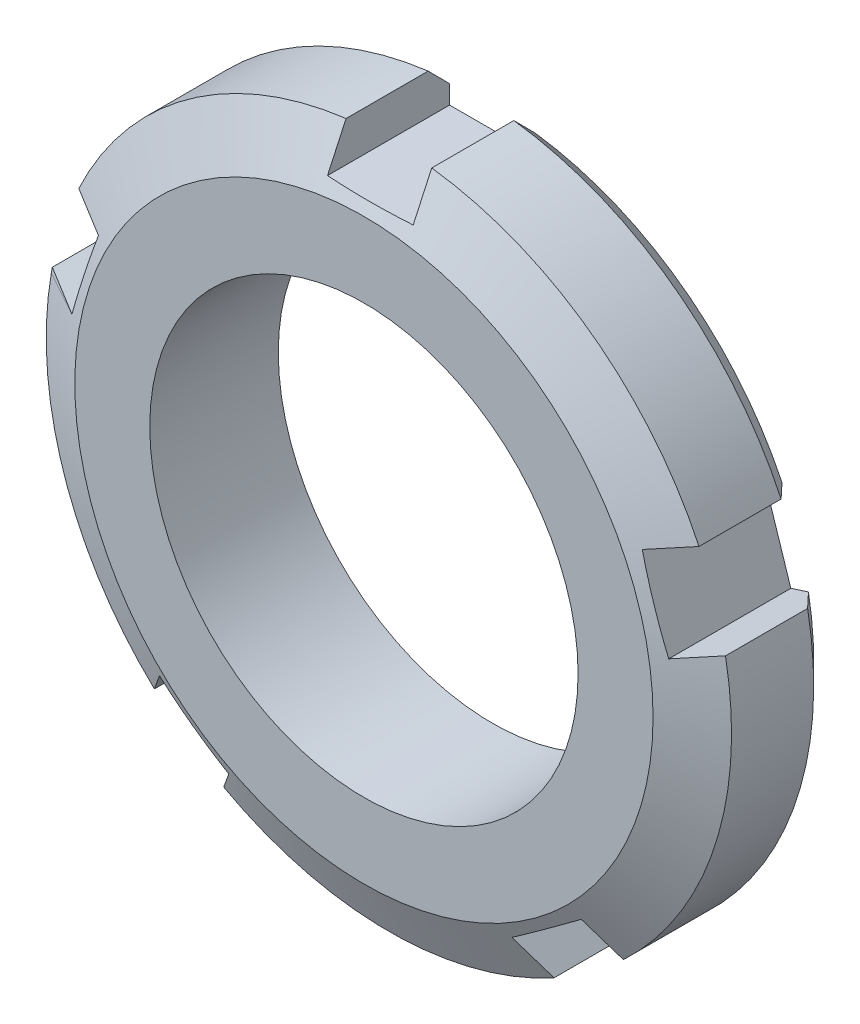
SolidWorks part; units mm, degrees
ref_plane "Front Plane" through (0, 0, 0) normal (0, 0, 1) x (1, 0, 0)
ref_plane "Top Plane" through (0, 0, 0) normal (0, 1, 0) x (1, 0, 0)
ref_plane "Right Plane" through (0, 0, 0) normal (1, 0, 0) x (0, 0, -1)
sketch "Sketch1" plane through (0, 0, 0) normal (1, 0, 0) x (0, 0, -1)
  line L0 (-16.3452, 0) -> (34.4162, 0) construction
  line L1 (0, 10) -> (6, 10)
  line L2 (6, 10) -> (6, 15)
  line L3 (6, 15) -> (5, 16)
  line L4 (5, 16) -> (1.1658, 16)
  line L5 (1.1658, 16) -> (0, 13.5)
  line L6 (0, 13.5) -> (0, 10)
  dimension "D1" = 20
  dimension "D2" = 32
  dimension "D3" = 6
  dimension "D4" = 45
  dimension "D5" = 25
  dimension "D6" = 2.5
  dimension "D7" = 1
revolve "Revolve1" add sketch "Sketch1" angle 360 about L0
sketch "Sketch2" plane through (0, 0, 0) normal (0, 0, 1) x (1, 0, 0)
  line L1 (-2, 16) -> (2, 16)
  line L2 (-2, 16) -> (-2, 14)
  line L3 (-2, 14) -> (2, 14)
  line L4 (2, 16) -> (2, 14)
  circle A0 centre (0, 0) radius 16 construction
  point P4 (0, 14)
  dimension "D1" = 4
  dimension "D2" = 2
extrude "Cut-Extrude1" cut sketch "Sketch2" against normal through all
pattern_circular "CirPattern1" count 5 over 360 about axis through (0, 0, 16.3452) along (0, 0, 1) of "Cut-Extrude1" reverse direction yes
equation "\"D1@Sketch1\"=\"d_int_ecrou_encouch_matrice\""
equation "\"D3@Sketch1\"=\"b_ecrou_encouch_matrice\""
equation "\"D1@Sketch2\"=\"s_ecrou_encouch_matrice\""
equation "\"D2@Sketch2\"=\"s_ecrou_encouch_matrice\"/2"
equation "\"d_ext_rouleau\"= 90"
equation "\"epaisseur_rouleau\"=80"
equation "\"alesage-rouleau\"= 52"
equation "\"jeu_dent_rouleau\"= 2"
equation "\"profondeur_dent_rouleau\"=4"
equation "\"n_dent_roueau\"= 15"
equation "\"d_ext_roulement_rouleau\"= 42"
equation "\"d_int_roulement_rouleau\"= 20"
equation "\"B_roulement_rouleau\"= 12"
equation "\"r_roulement_rouleau\"= 0.6"
equation "\"d_bille_roulement_rouleau\"= 8"
equation "\"F_anneau_alesage_rouleau\"=1.85"
equation "\"G_anneau_alesage_rouleau\"=47.5"
equation "\"K_anneau_alesage_rouleau\"=3.75"
equation "\"d_vis_flasque_rouleau\"=5"
equation "\"l-x_vis_flasque_rouleau\"=4"
equation "\"g_anneau_arbre_rouleau\"=19"
equation "\"f_anneau_arbre_rouleau\"=1.3"
equation "\"k_anneau_arbre_rouleau\"=1.5"
equation "\"h_matrice\"= 18"
equation "\"d_matrice\"= 220"
equation "\"d_granulat\"= 8"
equation "\"zone_vide_matrice\" = 48"
equation "\"d_alesage_matrice\"=20"
equation "\"a_clavette_alesage_matrice\"=6"
equation "\"entrax_vis_rouleau\"=65"
equation "\"B_roulement_matrice\"= 12"
equation "\"d_ext_roulement_matrice\"= 42"
equation "\"d_int_roulement_matrice\"= 20"
equation "\"r_roulement_matrice\"= 1"
equation "\"h_epaulement_arbre_matrice\" = 100"
equation "\"h_polie_matrice\" = 40"
equation "\"l_arbre_matrice\" = 300"
equation "\"d_int_ecrou_encouch_matrice\" = 20"
equation "\"d_ext_ecrou_encouch_matrice\" = 32"
equation "\"b_ecrou_encouch_matrice\" = 6"
equation "\"s_ecrou_encouch_matrice\" = 4"
equation "\"D2@Sketch1\"=\"d_ext_ecrou_encouch_matrice\""
equation "\"G_ecrou_encouch_matrice\" = 1"
equation "\"E_ecrou_encouch_matrice\" = 4"
